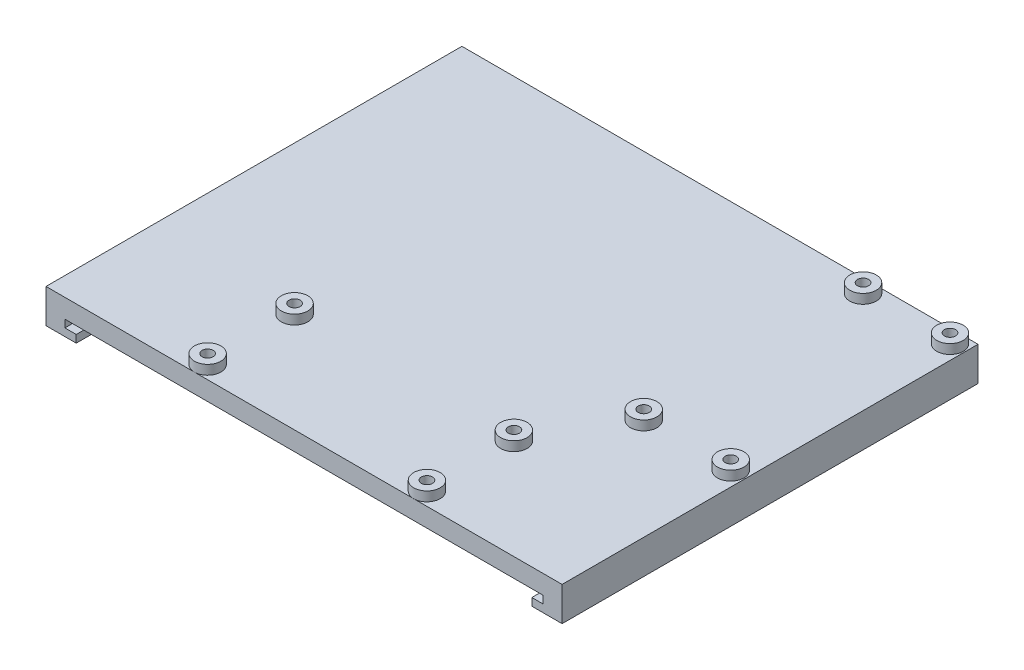
SolidWorks part; units mm, degrees
ref_plane "Front Plane" through (0, 0, 0) normal (0, 0, 1) x (1, 0, 0)
ref_plane "Top Plane" through (0, 0, 0) normal (0, 1, 0) x (1, 0, 0)
ref_plane "Right Plane" through (0, 0, 0) normal (1, 0, 0) x (0, 0, -1)
sketch "Sketch1" plane through (0, 0, 0) normal (0, 1, 0) x (1, 0, 0)
  line L0 (63.25, -50) -> (63.25, -55)
  line L1 (-63.25, 50) -> (63.25, 50)
  line L2 (-63.25, 50) -> (-63.25, -50)
  line L3 (-63.25, -50) -> (63.25, -50)
  line L4 (63.25, 50) -> (63.25, -50)
  line L5 (-63.25, 50) -> (63.25, -50) construction
  line L6 (-63.25, -50) -> (63.25, 50) construction
  line L7 (-68.25, 55) -> (68.25, 55)
  line L8 (-68.25, 55) -> (-68.25, -55)
  line L9 (-68.25, -55) -> (68.25, -55)
  line L10 (68.25, 55) -> (68.25, -55)
  line L11 (-68.25, 55) -> (68.25, -55) construction
  line L12 (-68.25, -55) -> (68.25, 55) construction
  line L13 (-63.25, -50) -> (-63.25, -55)
  point P0 (0, 0)
  point P6 (0, 0)
  dimension "D1" = 100
  dimension "D2" = 126.5
  dimension "D3" = 5
  dimension "D4" = 5
extrude "Boss-Extrude1" add sketch "Sketch1" along normal blind 5 contours L4 L1 L2 L3 | L13 L2 L1 L4 L0 L9 L10 L7 L8 | L3 L13 L9 L0 region at (65.0031, 0, 0) region at (0, 0, 52.5) region at (0, 0, 0)
extrude "Boss-Extrude2" add sketch "Sketch1<4>" against normal blind 4 contours L13 L2 L1 L4 L0 L9 L10 L7 L8 region at (65.0031, 0, 0)
sketch "Sketch1<4>" plane through (0, 0, 0) normal (0, 1, 0) x (1, 0, 0) same geometry as "Sketch1"
sketch "Sketch2" plane through (0, -4, 0) normal (0, -1, 0) x (1, 0, 0)
  line L0 (-60.25, 55) -> (-60.25, -47)
  line L1 (-63.25, 55) -> (63.25, 55) construction
  line L2 (-60.25, -47) -> (60.25, -47)
  line L3 (60.25, -47) -> (60.25, 55)
  line L4 (-63.25, -50) -> (-63.25, 55) construction
  line L5 (-63.25, -50) -> (63.25, -50) construction
  line L6 (63.25, -50) -> (63.25, 55) construction
  line L7 (-63.25, 55) -> (-63.25, -50)
  line L8 (-63.25, -50) -> (63.25, -50)
  line L9 (63.25, -50) -> (63.25, 55)
  line L10 (63.25, 55) -> (60.25, 55)
  line L11 (-60.25, 55) -> (-63.25, 55)
  dimension "D1" = 3
  dimension "D2" = 3
  dimension "D3" = 3
extrude "Boss-Extrude3" add sketch "Sketch2" against normal blind 2
sketch "Sketch3" plane through (0, 5, 0) normal (0, 1, 0) x (1, 0, 0)
  line L0 (-68.25, -55) -> (68.25, -55) construction
  line L1 (32.5, -55) -> (-32.5, -55)
  line L2 (32.5, -55) -> (32.5, -25)
  line L3 (32.5, -25) -> (-32.5, -25)
  line L4 (-32.5, -55) -> (-32.5, -25)
  line L5 (32.5, -55) -> (-32.5, -25) construction
  line L6 (32.5, -25) -> (-32.5, -55) construction
  line L11 (67.9214, 54.9254) -> (67.9214, -10.0746)
  line L12 (67.9214, 54.9254) -> (37.9214, 54.9254)
  line L14 (-68.25, 55) -> (-68.25, -55) construction
  line L15 (37.9214, 54.9254) -> (37.9214, -10.0746)
  line L16 (67.9214, -10.0746) -> (37.9214, -10.0746)
  line L17 (67.9214, 54.9254) -> (37.9214, -10.0746) construction
  line L18 (37.9214, 54.9254) -> (67.9214, -10.0746) construction
  circle A0 centre (29, -51.5) radius 3.5
  circle A1 centre (29, -28.5) radius 3.5
  circle A2 centre (-29, -51.5) radius 3.5
  circle A3 centre (-29, -28.5) radius 3.5
  circle A8 centre (-29, -28.5) radius 1.475
  circle A9 centre (-29, -51.5) radius 1.25
  circle A10 centre (-29, -28.5) radius 1.25
  circle A11 centre (29, -28.5) radius 1.475
  circle A12 centre (29, -28.5) radius 1.25
  circle A13 centre (29, -51.5) radius 1.475
  circle A14 centre (29, -51.5) radius 1.25
  circle A15 centre (-29, -51.5) radius 1.475
  circle A25 centre (64.4214, 51.4254) radius 3.5
  circle A26 centre (41.4214, 51.4254) radius 3.5
  circle A27 centre (64.4214, -6.5746) radius 3.5
  circle A28 centre (41.4214, -6.5746) radius 3.5
  circle A29 centre (41.4214, -6.5746) radius 1.475
  circle A30 centre (64.4214, -6.5746) radius 1.25
  circle A31 centre (41.4214, -6.5746) radius 1.25
  circle A32 centre (41.4214, 51.4254) radius 1.475
  circle A33 centre (41.4214, 51.4254) radius 1.25
  circle A34 centre (64.4214, 51.4254) radius 1.475
  circle A35 centre (64.4214, 51.4254) radius 1.25
  circle A36 centre (64.4214, -6.5746) radius 1.475
  point P0 (0, -40)
  point P16 (52.9214, 22.4254)
  dimension "D5" = 3.5
  dimension "D7" = 7
  dimension "D8" = 7
  dimension "D9" = 7
  dimension "D10" = 7
  dimension "D17" = 65
  dimension "D21" = 7
  dimension "D22" = 7
  dimension "D23" = 7
  dimension "D33" = 2.95
  dimension "D35" = 2.95
  dimension "D36" = 2.5
  dimension "D37" = 2.5
  dimension "D38" = 2.95
  dimension "D39" = 2.95
  dimension "D40" = 2.5
  dimension "D41" = 2.95
  dimension "D42" = 2.5
  dimension "D43" = 2.5
  dimension "D44" = 2.95
  dimension "D24" = 7
  dimension "D30" = 2.95
  dimension "D31" = 2.5
  dimension "D32" = 2.5
  dimension "D34" = 2.95
  dimension "D1" = 65
  dimension "D2" = 0
  dimension "D3" = 30
  dimension "D4" = 0
  dimension "D6" = 3.5
  dimension "D11" = 3.5
  dimension "D12" = 3.5
  dimension "D13" = 3.5
  dimension "D14" = 3.5
  dimension "D15" = 3.5
  dimension "D16" = 3.5
  dimension "D18" = 30
  dimension "D19" = 3.5
  dimension "D20" = 3.5
  dimension "D25" = 3.5
  dimension "D26" = 3.5
  dimension "D27" = 3.5
  dimension "D28" = 3.5
  dimension "D29" = 3.5
extrude "Boss-Extrude4" add sketch "Sketch3" along normal blind 2.5 contours A3 | A2 | A1 | A0 | A26 | A25 | A27 | A28 L2 region at (26.5951, 5, 49.0951) region at (-31.4049, 5, 53.9049) region at (26.5951, 5, 30.9049) region at (-31.4049, 5, 26.0951) region at (62.0165, 5, -49.0206) region at (66.8263, 5, 8.9794) region at (43.8263, 5, -53.8303) region at (39.0165, 5, 8.9794)
extrude "Cut-Extrude1" cut sketch "Sketch3<6>" against normal blind 2.5 contours A34 | A14 | A12 | A9 | A10 region at (-29, 5, 51.5) region at (-29, 5, 28.5) region at (29, 5, 28.5) region at (29, 5, 51.5) region at (62.9881, 5, -51.4254)
sketch "Sketch3<6>" plane through (0, 5, 0) normal (0, 1, 0) x (1, 0, 0) same geometry as "Sketch3"
